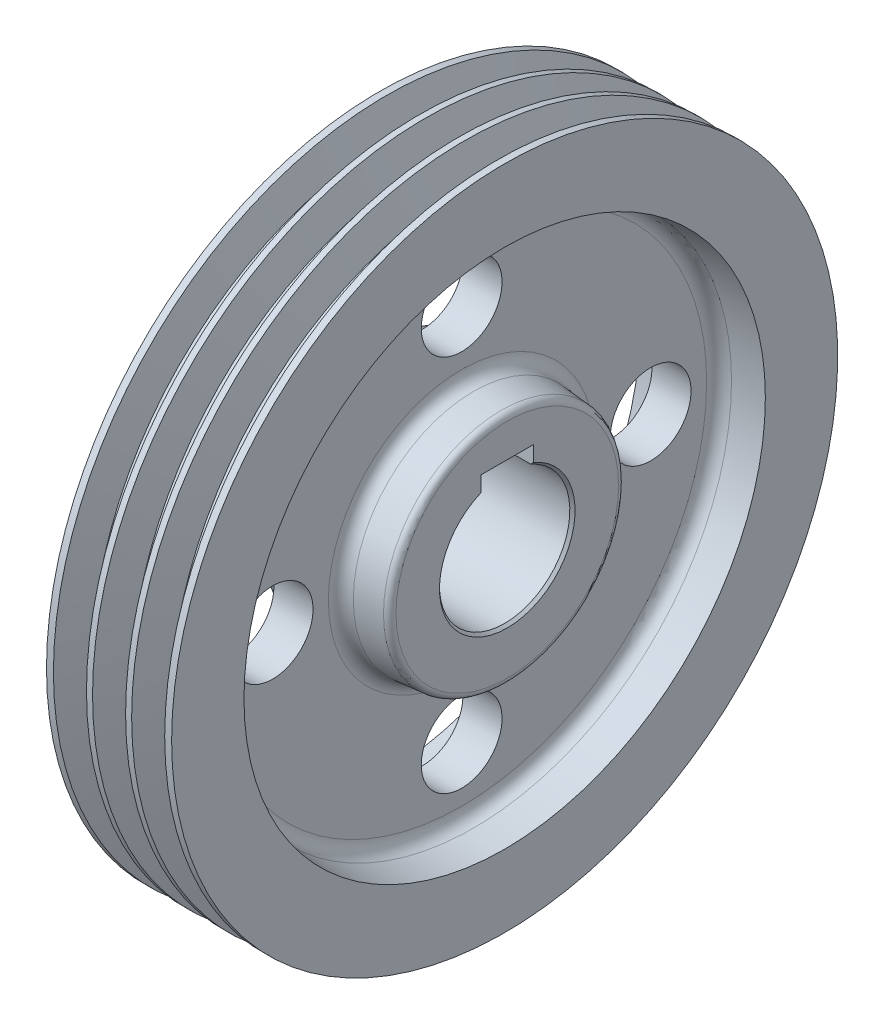
SolidWorks part; units mm, degrees
ref_plane "前视基准面" through (0, 0, 0) normal (0, 0, 1) x (1, 0, 0)
ref_plane "上视基准面" through (0, 0, 0) normal (0, 1, 0) x (1, 0, 0)
ref_plane "右视基准面" through (0, 0, 0) normal (1, 0, 0) x (0, 0, -1)
sketch "草图1" plane through (0, 0, 0) normal (0, 0, 1) x (1, 0, 0)
  line L0 (0, 0) -> (64.8368, 0) construction
  line L1 (-1, 25) -> (-1, 45)
  line L2 (0, 127.75) -> (48, 127.75)
  line L3 (48, 127.75) -> (48, 100)
  line L4 (-1, 45) -> (-30, 45) construction
  line L5 (16.5, 46.5311) -> (16.5, 98.5564)
  line L6 (49, 25) -> (-1, 25)
  line L7 (2.6592, 127.75) -> (6.1599, 116.3) construction
  line L8 (6.1599, 116.3) -> (11.8401, 116.3) construction
  line L9 (11.8401, 116.3) -> (15.3408, 127.75) construction
  line L10 (0, 125) -> (48, 125) construction
  line L11 (9, 116.3) -> (9, 25) construction
  line L12 (44, 100) -> (0, 100) construction
  line L13 (48, 100) -> (79, 100) construction
  line L14 (31.5, 98.5564) -> (31.5, 46.5311)
  line L15 (5, 45) -> (49, 45) construction
  line L16 (24, 25) -> (24, 127.75) construction
  line L17 (49, 45) -> (49, 25)
  line L18 (0, 100) -> (0, 127.75)
  line L19 (16.5, 88) -> (31.5, 88) construction
  line L20 (16.5, 57) -> (31.5, 57) construction
  line L21 (48, 100) -> (48, 88) construction
  line L22 (48, 88) -> (31.5, 88) construction
  line L23 (31.5, 57) -> (49, 57) construction
  line L24 (49, 57) -> (49, 45) construction
  line L25 (31.5, 98.5564) -> (48, 100)
  line L26 (16.5, 98.5564) -> (0, 100)
  line L27 (16.5, 46.5311) -> (-1, 45)
  line L28 (31.5, 46.5311) -> (49, 45)
  point P17 (3.5, 125)
  point P18 (14.5, 125)
  dimension "d2" = 200
  dimension "L" = 50
  dimension "B" = 48
  dimension "d" = 50
  dimension "d1" = 90
  dimension "D3" = 5
  dimension "D4" = 5
  dimension "dd" = 250
  dimension "f" = 9
  dimension "槽轮角" = 34
  dimension "bd" = 11
  dimension "hf" = 8.7
  dimension "ha" = 2.75
  dimension "da" = 255.5
  dimension "S" = 15
  dimension "S2" = 12
revolve "旋转1" add sketch "草图1" angle 360 about L0
sketch "草图2" plane through (0, 0, 0) normal (0, 0, 1) x (1, 0, 0)
  line L0 (11.8401, 116.3) -> (15.3408, 127.75) construction
  line L1 (6.1599, 116.3) -> (11.8401, 116.3) construction
  line L2 (2.6592, 127.75) -> (6.1599, 116.3) construction
  line L3 (11.8401, 116.3) -> (15.3408, 127.75)
  line L4 (6.1599, 116.3) -> (11.8401, 116.3)
  line L5 (2.6592, 127.75) -> (6.1599, 116.3)
  line L6 (2.6592, 127.75) -> (15.3408, 127.75)
  line L7 (0, 0) -> (123, 0) construction
revolve "切除-旋转1" cut sketch "草图2" angle 360 about L7
pattern_linear "轮槽数" count 3 spacing 15 along (1, 0, 0) of "切除-旋转1"
chamfer "倒角1" distance 1 angle 45 2 edges at (-1, 0, 25) (49, 0, 25)
sketch "草图4" plane through (-1, 0, 0) normal (-1, 0, 0) x (0, 0, 1)
  line L1 (-10, 22.9129) -> (10, 22.9129)
  line L2 (-10, 22.9129) -> (-10, 29.9)
  line L3 (-10, 29.9) -> (10, 29.9)
  line L4 (10, 22.9129) -> (10, 29.9)
  circle A0 centre (0, 0) radius 25 construction
  point P6 (5.1, 29.9)
  dimension "键槽高度" = 29.9
  dimension "键槽宽度" = 20
  dimension "t1" = 4.9
extrude "切除-拉伸1" cut sketch "草图4" against normal through all
fillet "圆角1" radius 5 4 edges at (31.5, 0, 98.5564) (16.5, 0, 46.5311) (16.5, 0, 98.5564) (31.5, 0, 46.5311)
fillet "圆角2" radius 2.5 2 edges at (49, 0, 45) (-1, 0, 45)
sketch "草图5" plane through (0, 0, 0) normal (1, 0, 0) x (0, 0, -1)
  line L0 (0, 116.3) -> (0, 25) construction
  circle A0 centre (0, 72.5) radius 15.5
extrude "切除-拉伸2" cut sketch "草图5" along normal through all
pattern_circular "圆孔个数" count 4 over 360 of "切除-拉伸2"
equation "\"B@草图1\" =  ( \"z@轮槽数\" - 1 )  * \"e@轮槽数\" +2 *  \"f@草图1\""
equation "\"键槽高度@草图4\" = \"d@草图1\" / 2 + \"t1@草图4\""
